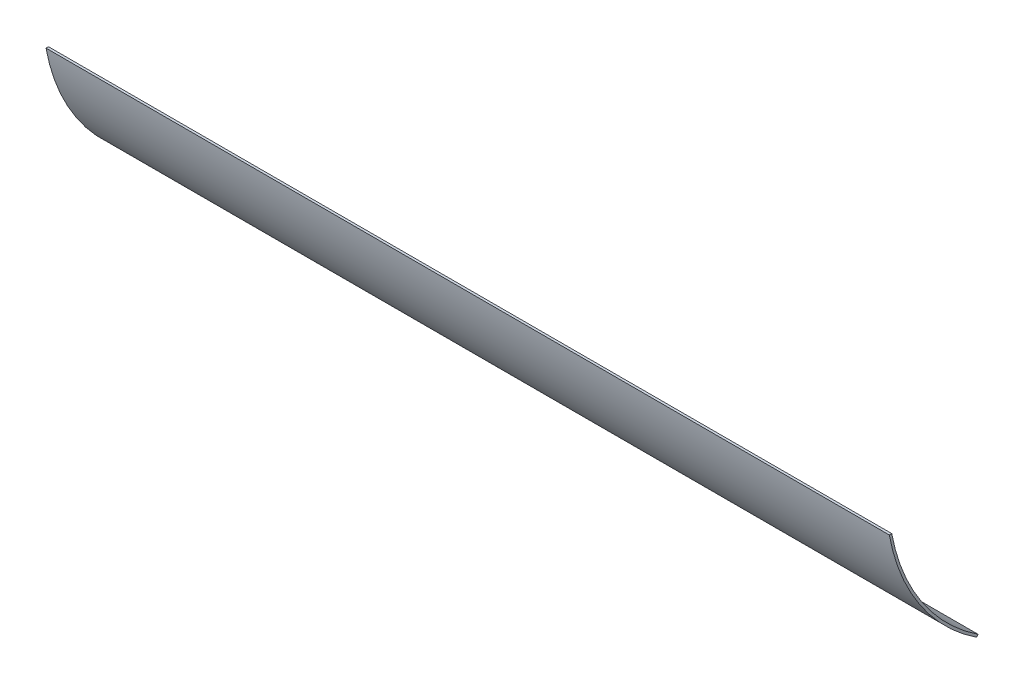
SolidWorks part; units mm, degrees
material "Acrylic (Medium-high impact)"
ref_plane "Front Plane" through (0, 0, 0) normal (0, 0, 1) x (1, 0, 0)
ref_plane "Top Plane" through (0, 0, 0) normal (0, 1, 0) x (1, 0, 0)
ref_plane "Right Plane" through (0, 0, 0) normal (1, 0, 0) x (0, 0, -1)
sketch "Sketch1" plane through (0, 0, 0) normal (1, 0, 0) x (0, 0, -1)
  line L1 (-129.9041, -23.876) -> (-131.5178, -23.876)
  line L2 (-72.7541, -110.236) -> (-73.6285, -111.5609)
  arc A0 (-129.9041, -23.876) -> (-72.7541, -110.236) centre (0, 0) ccw
  arc A1 (-131.5178, -23.876) -> (-73.6285, -111.5609) centre (0, 0) ccw
  point P4 (-131.9937, -4.774)
  point P5 (-133.5822, -4.774)
  point P7 (-131.6798, -10.1851)
  point P8 (-131.1629, -15.5138)
  dimension "D1" = 132.08
  dimension "D2" = 1.5875
  dimension "D3" = 57.15
  dimension "D4" = 23.876
extrude "Boss-Extrude1" add sketch "Sketch1" along normal blind 558.8
